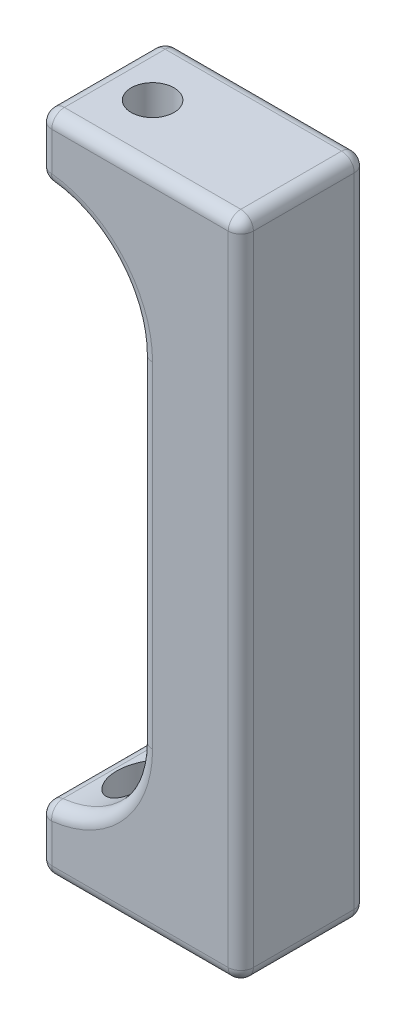
SolidWorks part; units mm, degrees
ref_plane "Front Plane" through (0, 0, 0) normal (0, 0, 1) x (1, 0, 0)
ref_plane "Top Plane" through (0, 0, 0) normal (0, 1, 0) x (1, 0, 0)
ref_plane "Right Plane" through (0, 0, 0) normal (1, 0, 0) x (0, 0, -1)
sketch "Sketch1" plane through (0, 0, 0) normal (0, 0, 1) x (1, 0, 0)
  line L0 (4, 0) -> (-38.3542, 0) construction
  line L1 (-4, -26.3) -> (4, -26.3)
  line L2 (-4, -26.3) -> (-4, 26.3)
  line L3 (-4, 26.3) -> (4, 26.3)
  line L4 (4, -26.3) -> (4, 26.3)
  line L5 (-4, -26.3) -> (4, 26.3) construction
  line L6 (-4, 26.3) -> (4, -26.3) construction
  line L7 (-4, 26.3) -> (-12, 26.3)
  line L8 (-4, 26.3) -> (-4, 21.3)
  line L9 (-4, 21.3) -> (-12, 21.3)
  line L10 (-12, 26.3) -> (-12, 21.3)
  line L11 (-4, -21.3) -> (-12, -21.3)
  line L12 (-12, -26.3) -> (-12, -21.3)
  line L13 (-4, -26.3) -> (-12, -26.3)
  line L14 (-4, -26.3) -> (-4, -21.3)
  point P0 (0, 0)
  dimension "D1" = 8
  dimension "D2" = 52.6
  dimension "D3" = 5
  dimension "D4" = 8
extrude "Boss-Extrude1" add sketch "Sketch1" along normal blind 10 contours L7 L10 L9 L2 | L1 L4 L3 L2 | L13 L2 L11 L12 region at (0, 0, 0) region at (-8, -23.8, 0) region at (-8, 23.8, 0)
sketch "Sketch2" plane through (0, 26.3, 0) normal (0, 1, 0) x (1, 0, 0)
  line L0 (-12, -5) -> (-4, -5) construction
  line L1 (-8, 0) -> (-8, -10) construction
  line L4 (-4, 0) -> (-12, 0)
  line L5 (-12, 0) -> (-12, -10)
  line L6 (-12, -10) -> (-4, -10)
  line L7 (-4, -10) -> (-4, 0)
  line L8 (-4, 0) -> (-12, 0)
  line L9 (-12, 0) -> (-12, -10)
  line L10 (-12, -10) -> (-4, -10)
  line L11 (-4, -10) -> (-4, 0)
  circle A0 centre (-8, -5) radius 1.7
  dimension "D2" = 3.4
  dimension "D1" = 0
extrude "Cut-Extrude1" cut sketch "Sketch2" against normal through all contours A0 region at (-8, 26.3, 5)
sketch "Sketch3" plane through (0, -21.3, 0) normal (0, 1, 0) x (1, 0, 0)
  circle A0 centre (-8, -5) radius 2.85
  dimension "D1" = 5.7
extrude "Cut-Extrude2" cut sketch "Sketch3" against normal blind 2.5 and the other way blind 40
fillet "Fillet1" radius 8 2 edges at (-4, 21.3, 5) (-4, -21.3, 5)
fillet "Fillet2" radius 1 22 edges at (-12, 26.3, 5) (-12, 21.3, 5) (-12, -21.3, 5) (-12, -26.3, 5) (-12, 23.8, 0) (-6.3431, 18.9569, 0) (-4, 0, 0) (-6.3431, -18.9569, 0) (-12, -23.8, 0) (-4, -26.3, 0) (-4, 26.3, 0) (4, -26.3, 5) (4, 26.3, 5) (4, 0, 0) (4, 0, 10) (-4, -26.3, 10) (-12, -23.8, 10) (-6.3431, -18.9569, 10) (-4, 0, 10) (-6.3431, 18.9569, 10) (-12, 23.8, 10) (-4, 26.3, 10)
